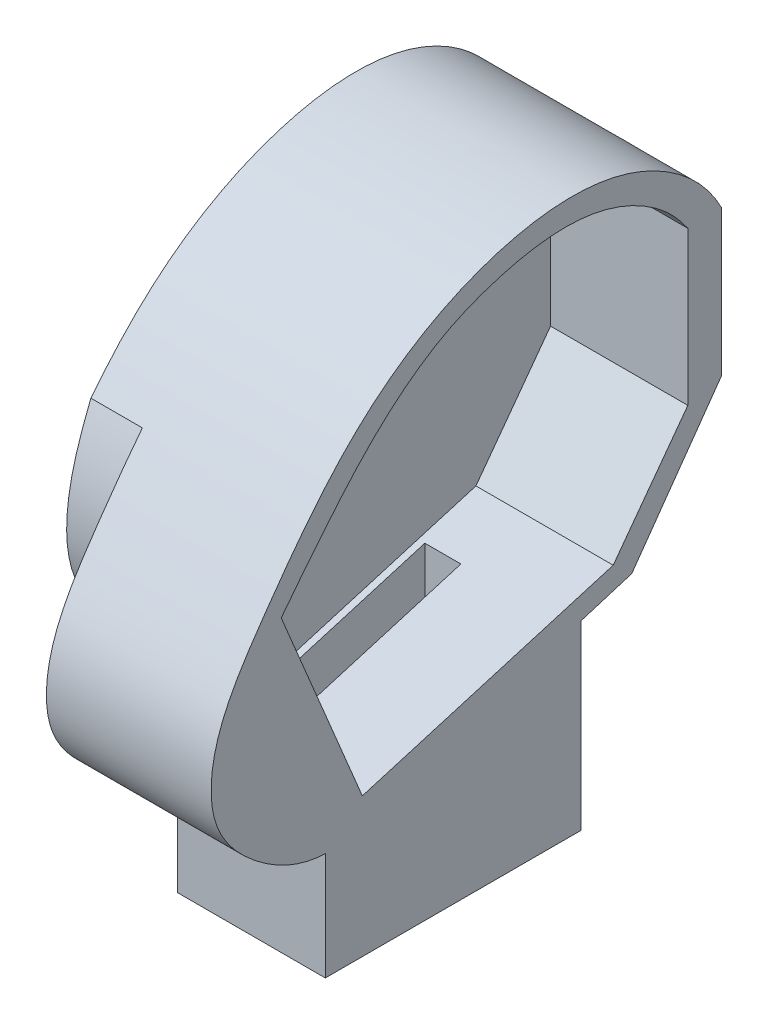
SolidWorks part; units mm, degrees
ref_plane "Front Plane" through (0, 0, 0) normal (0, 0, 1) x (1, 0, 0)
ref_plane "Top Plane" through (0, 0, 0) normal (0, 1, 0) x (1, 0, 0)
ref_plane "Right Plane" through (0, 0, 0) normal (1, 0, 0) x (0, 0, -1)
sketch "Sketch1" plane through (0, 0, 0) normal (1, 0, 0) x (0, 0, -1)
  line L1 (0, 0) -> (-37.846, 0)
  line L2 (0, 0) -> (0, 33.782)
  line L3 (0, 33.782) -> (-37.846, 33.782)
  line L4 (-37.846, 0) -> (-37.846, 33.782)
  dimension "D1" = 33.782
  dimension "D2" = 37.846
extrude "Boss-Extrude1" add sketch "Sketch1" along normal blind 32.004
sketch "Sketch2" plane through (0, 0, 37.846) normal (0, 0, 1) x (1, 0, 0)
  line L0 (0, 33.782) -> (0, 0) construction
  line L11 (32.004, 0) -> (0, 0) construction
  line L12 (10.16, 0) -> (0, 0)
  line L13 (10.16, 0) -> (10.16, 33.782)
  line L14 (10.16, 33.782) -> (0, 33.782)
  line L15 (0, 0) -> (0, 33.782)
  point P0 (0, 0)
  point P4 (0, 0)
  dimension "D1" = 10.16
extrude "Cut-Extrude1" cut sketch "Sketch2" against normal up to surface (37.846 mm away) up to face at (16.002, 16.891, 0)
sketch "Sketch3" plane through (32.004, 0, 0) normal (1, 0, 0) x (0, 0, -1)
  line L0 (-35.2417, 16.1245) -> (7.5067, 29.1494)
  line L1 (7.5067, 29.1494) -> (21.3316, 48.6306)
  line L2 (-51.7111, 23.6049) -> (19.9, 70.959) construction
  spline S0 degree 3 poles (-35.2417, 16.1245) (-39.9478, 15.3491) (-47.2639, 18.4414) (-54.7216, 26.5969) (-55.1114, 38.9449) (-45.3425, 53.5257) (-33.0028, 70.1382) (-13.8868, 81.1513) (5.1507, 83.3825) (23.2757, 71.7348) (24.9587, 56.0405) (21.3316, 48.6306) knots 0 0 0 0 0.087691 0.15218 0.20347 0.316563 0.484811 0.607203 0.740718 0.837611 1 1 1 1
  dimension "D1" = 85.852
extrude "Boss-Extrude2" add sketch "Sketch3" against normal blind 32.004
sketch "Sketch12" plane through (0, 0, 0) normal (-1, 0, 0) x (0, 0, 1)
  line L0 (-11.9892, 69.551) -> (51.4002, 22.8416) construction
  line L1 (0, 26.8622) -> (30.459, 27.7535)
  line L2 (37.846, 15.948) -> (37.846, 0)
  line L3 (37.846, 0) -> (0, 0)
  line L4 (0, 0) -> (0, 26.8622)
  spline S0 degree 3 poles (40.5405, 59.6654) (42.9098, 53.84) (47.2039, 40.1584) (37.5508, 28.1814) (30.459, 27.7535) knots 0 0 0 0 0.50313 1 1 1 1
  spline S1 degree 3 poles (-21.3316, 48.6306) (-24.9587, 56.0405) (-23.2757, 71.7348) (-5.1507, 83.3825) (13.8868, 81.1513) (33.0028, 70.1382) (45.3425, 53.5257) (55.1114, 38.9449) (54.7216, 26.5969) (47.2639, 18.4414) (39.9478, 15.3491) (35.2417, 16.1245) knots 0 0 0 0 0.162389 0.259282 0.392797 0.515189 0.683437 0.79653 0.84782 0.912309 1 1 1 1 construction
  spline S2 degree 3 poles (37.846, 15.948) (46.0715, 11.3266) (62.4127, 24.6896) (57.3541, 47.5971) (48.0434, 61.6223) (40.5405, 59.6654) knots 0 0 0 0 0.367769 0.695373 1 1 1 1
  point P8 (0, 0)
  point P10 (0, 0)
  point P17 (0, 0)
  point P20 (0, 0)
  point P25 (0, 0)
  dimension "D1" = 78.74
extrude "Cut-Extrude12" cut sketch "Sketch12" against normal blind 7.62
sketch "Sketch9" plane through (0, 0, 0) normal (0, 1, 0) x (1, 0, 0)
  line L3 (0, 18.559) -> (32.004, 20.7969)
  line L4 (32.004, -54.7446) -> (32.004, 23.4787) construction
  line L9 (0, 23.4787) -> (32.004, 23.4787)
  line L10 (0, 23.4787) -> (0, 18.559)
  line L12 (32.004, 23.4787) -> (32.004, 20.7969)
extrude "Cut-Extrude6" cut sketch "Sketch9" against normal through all and the other way through all contours L3 L12 L9 L10
sketch "Sketch5" plane through (32.004, 0, 0) normal (1, 0, 0) x (0, 0, -1)
  line L0 (-47.0595, 27.2029) -> (16.1226, 68.8839) construction
  line L1 (-32.3674, 20.6066) -> (4.7639, 31.6044)
  line L2 (4.7639, 31.6044) -> (15.8089, 46.569)
  line L3 (15.8089, 69.2651) -> (15.8089, 46.569)
  line L4 (-32.3674, 20.6066) -> (-44.3727, 49.411)
  spline S0 degree 3 poles (15.8089, 69.2651) (14.9408, 70.5451) (11.2983, 74.8054) (1.2724, 79.6372) (-10.6372, 77.7837) (-22.1065, 73.2382) (-31.968, 65.0943) (-39.0318, 56.1793) (-43.3868, 50.7492) (-44.3727, 49.411) knots 0.161487 0.161487 0.161487 0.161487 0.195181 0.282931 0.393082 0.449623 0.554918 0.668374 0.704281 0.704281 0.704281 0.704281
  dimension "D1" = 75.692
extrude "Cut-Extrude2" cut sketch "Sketch5" against normal blind 20.32
sketch "Sketch8" plane through (32.004, 0, 0) normal (1, 0, 0) x (0, 0, -1)
  line L0 (-42.5367, 19.4528) -> (16.3785, 58.3765) construction
  line L1 (-49.4198, 20.3763) -> (22.2283, 67.6744) construction
  line L2 (-41.588, 26.4661) -> (14.1677, 63.2604) construction
  line L3 (-43.2869, 29.7532) -> (12.4492, 66.5769) construction
  line L4 (-42.0219, 30.9666) -> (9.4868, 64.9733) construction
  line L5 (-29.6838, 25.6194) -> (3.1665, 35.6397)
  line L6 (3.1665, 35.6397) -> (11.3672, 46.6708)
  line L7 (-32.3674, 20.6066) -> (4.7639, 31.6044)
  line L8 (4.7639, 31.6044) -> (15.8089, 46.569)
  line L9 (15.9524, 70.6134) -> (15.8089, 46.569)
  line L10 (15.8089, 46.569) -> (15.8089, 69.2651) construction
  line L11 (12.5052, 65.7075) -> (12.5052, 48.6114)
  line L12 (-39.5488, 49.391) -> (-29.6838, 25.6194)
  line L13 (-44.3727, 49.411) -> (-32.3674, 20.6066) construction
  spline S0 degree 3 poles (-29.6838, 25.6194) (-34.4484, 24.5304) (-43.0649, 28.7008) (-44.7141, 39.5686) (-38.4282, 52.5293) (-28.7004, 64.0164) (-13.8108, 73.3227) (-0.5324, 75.8006) (9.0557, 71.168) (11.9383, 66.8263) (12.5052, 65.7075) knots 0 0 0 0 0.124401 0.195531 0.259778 0.471134 0.585671 0.701552 0.801883 0.833636 0.833636 0.833636 0.833636
  spline S1 degree 3 poles (15.9524, 70.6134) (12.375, 75.2039) (0.0596, 82.062) (-24.0382, 75.5867) (-37.4169, 58.6534) (-50.3792, 45.0566) (-52.2244, 26.8478) (-39.5335, 17.9656) (-32.3674, 20.6066) knots 0.167615 0.167615 0.167615 0.167615 0.285518 0.450573 0.65048 0.7429 0.848871 1 1 1 1
  spline S2 degree 2 poles (12.5052, 48.6114) (12.0006, 47.5939) (11.3672, 46.6708) knots 0.980574 0.980574 0.980574 1 1 1
  point P20 (0, 0)
  point P29 (-40.2441, 47.933)
  point P36 (-39.9072, 48.6114)
  point P38 (-39.57, 49.3561)
  dimension "D1" = 70.612
  dimension "D2" = 85.852
  dimension "D3" = 66.802
  dimension "D4" = 66.802
  dimension "D5" = 61.722
  dimension "D6" = 4.445
sketch "Sketch10" plane through (0, 0, 0) normal (0, -1, 0) x (1, 0, 0)
  line L1 (12.7, 3.81) -> (18.034, 3.81)
  line L2 (12.7, 3.81) -> (12.7, 32.258)
  line L3 (12.7, 32.258) -> (18.034, 32.258)
  line L4 (18.034, 3.81) -> (18.034, 32.258)
  line L5 (32.004, 37.846) -> (10.16, 37.846) construction
  line L7 (32.004, 0) -> (10.16, 0) construction
  line L9 (10.16, 0) -> (10.16, 37.846) construction
  line L10 (32.004, 37.846) -> (32.004, 0) construction
  dimension "D1" = 2.54
  dimension "D2" = 5.588
  dimension "D3" = 13.97
  dimension "D4" = 3.81
extrude "Cut-Extrude7" cut sketch "Sketch10" against normal up to surface (29.0649 mm away) up to face at (21.844, 26.1055, 13.8017)
